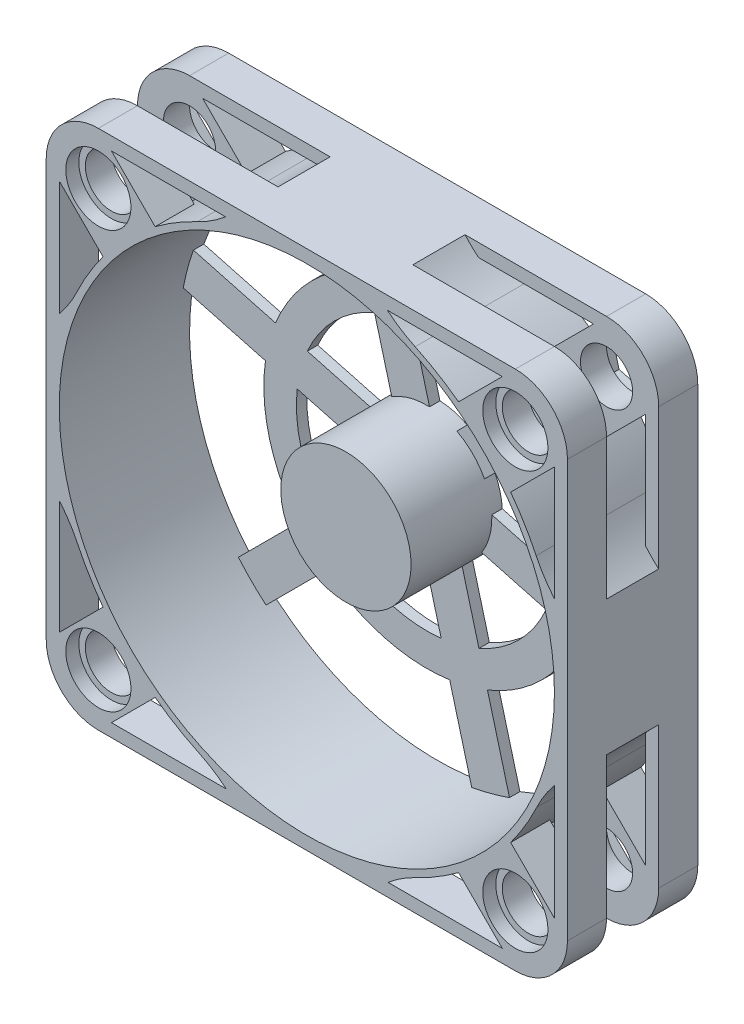
SolidWorks part; units mm, degrees
ref_plane "Plan de face" through (0, 0, 0) normal (0, 0, 1) x (1, 0, 0)
ref_plane "Plan de dessus" through (0, 0, 0) normal (0, 1, 0) x (1, 0, 0)
ref_plane "Plan de droite" through (0, 0, 0) normal (1, 0, 0) x (0, 0, -1)
sketch "Esquisse1" plane through (0, 0, 0) normal (0, 0, 1) x (1, 0, 0)
  line L0 (4.4333, 2.312) -> (14.4538, 12.3324)
  line L1 (16, -20) -> (-16, -20)
  line L2 (20, -16) -> (20, 16)
  line L3 (16, 20) -> (-16, 20)
  line L4 (-20, -16) -> (-20, 16)
  line L5 (20, -20) -> (-20, 20) construction
  line L6 (20, 20) -> (-20, -20) construction
  line L7 (2.312, 4.4333) -> (12.3324, 14.4538)
  line L8 (4.2189, -2.6834) -> (17.9071, -6.3511)
  line L9 (4.9954, 0.2144) -> (18.6835, -3.4533)
  line L10 (-0.2144, -4.9954) -> (3.4533, -18.6835)
  line L11 (2.6834, -4.2189) -> (6.3511, -17.9071)
  line L12 (-4.4333, -2.312) -> (-14.4538, -12.3324)
  line L13 (-2.312, -4.4333) -> (-12.3324, -14.4538)
  line L14 (-4.2189, 2.6834) -> (-17.9071, 6.3511)
  line L15 (-4.9954, -0.2144) -> (-18.6835, 3.4533)
  line L16 (0.2144, 4.9954) -> (-3.4533, 18.6835)
  line L17 (-2.6834, 4.2189) -> (-6.3511, 17.9071)
  arc A0 (-16, -20) -> (-20, -16) centre (-16, -16) cw
  arc A1 (16, -20) -> (20, -16) centre (16, -16) ccw
  arc A2 (20, 16) -> (16, 20) centre (16, 16) ccw
  arc A3 (-16, 20) -> (-20, 16) centre (-16, 16) ccw
  circle A4 centre (0, 0) radius 19
  circle A5 centre (-16, 16) radius 2
  circle A6 centre (16, 16) radius 2
  circle A7 centre (16, -16) radius 2
  circle A8 centre (-16, -16) radius 2
  circle A9 centre (0, 0) radius 5
  circle A10 centre (0, 0) radius 10
  circle A11 centre (0, 0) radius 12.5
  point P0 (0, 0)
  point P52 (0, 0)
  dimension "D3" = 4
  dimension "D4" = 38
  dimension "D5" = 4
  dimension "D6" = 4
  dimension "D7" = 4
  dimension "D8" = 4
  dimension "D9" = 10
  dimension "D12" = 25
  dimension "D13" = 20
  dimension "D1" = 40
  dimension "D2" = 40
  dimension "D10" = 3
  dimension "D11" = 6
extrude "Boss.-Extru.1" add sketch "Esquisse1" along normal blind 10 contours L3 A3 L4 A0 L1 A1 L2 A2 A8 A7 A6 A5 A4 | A11 L12 A4 L13 | L15 A11 L12 A10 | L12 A11 L13 A10 | L12 A10 L13 A9 | L13 A11 L10 A10 | L10 A11 L11 A10 | L10 A10 L11 A9 | A11 L10 A4 L11 | A9 | A11 L14 A4 L15 | L14 A11 L15 A10 | L14 A10 L15 A9 | L17 A11 L14 A10 | A11 L16 A4 L17 | L16 A11 L17 A10 | L16 A10 L17 A9 | L7 A11 L16 A10 | A11 L0 A4 L7 | L0 A10 L7 A9 | L0 A11 L7 A10 | L9 A11 L0 A10 | L8 A11 L9 A10 | A11 L8 A4 L9 | L11 A11 L8 A10 | L8 A10 L9 A9 region at (5.2629, 5.2629, 0) region at (0, 0, 0) region at (7.931, 7.931, 0) region at (10.651, 2.8539, 0) region at (7.1892, -1.9263, 0) region at (11.1193, 11.1193, 0) region at (2.8539, 10.651, 0) region at (10.8339, -2.9029, 0) region at (-1.9263, 7.1892, 0) region at (-2.9029, 10.8339, 0) region at (15.1892, -4.0699, 0) region at (7.797, -7.797, 0) region at (-4.0699, 15.1892, 0) region at (-7.797, 7.797, 0) region at (1.9263, -7.1892, 0) region at (2.9029, -10.8339, 0) region at (-7.1892, 1.9263, 0) region at (-10.8339, 2.9029, 0) region at (4.0699, -15.1892, 0) region at (-2.8539, -10.651, 0) region at (-15.1892, 4.0699, 0) region at (-10.651, -2.8539, 0) region at (-5.2629, -5.2629, 0) region at (-7.931, -7.931, 0) region at (-11.1193, -11.1193, 0) region at (0, -19.4343, 0)
sketch "Esquisse2" plane through (0, 0, 10) normal (0, 0, 1) x (1, 0, 0)
  circle A0 centre (0, 0) radius 19
  circle A1 centre (0, 0) radius 5
  dimension "D1" = 38
  dimension "D2" = 10
extrude "Enlèv. mat.-Extru.1" cut sketch "Esquisse2" against normal blind 9.2
sketch "Esquisse3" plane through (0, 0, 10) normal (0, 0, 1) x (1, 0, 0)
  line L0 (19, 15) -> (19, 4.3875)
  line L1 (20, -16) -> (20, 16) construction
  line L2 (4.3875, 19) -> (15, 19)
  line L3 (16, 20) -> (-16, 20) construction
  line L4 (15, 19) -> (11.6428, 15.6428)
  line L5 (7.7143, 9.8356) -> (12.3324, 14.4538) construction
  line L6 (19, 15) -> (15.6428, 11.6428)
  circle A0 centre (0, 0) radius 19.5
  arc A1 (15, 19) -> (19, 15) centre (15, 15) cw
  dimension "D1" = 39
  dimension "D4" = 4
  dimension "D2" = 1
  dimension "D3" = 1
extrude "Enlèv. mat.-Extru.2" cut sketch "Esquisse3" against normal blind 3 contours A0 L0 L6 | A0 L4 L2 region at (17.9389, 10.6636, 10) region at (10.6636, 17.9389, 10)
sketch "Esquisse4" plane through (0, 0, 10) normal (0, 0, 1) x (1, 0, 0)
  circle A0 centre (16, 16) radius 2.5
  dimension "D1" = 5
extrude "Enlèv. mat.-Extru.3" cut sketch "Esquisse4" against normal blind 1
pattern_circular "Répétition circulaire1" count 4 over 360 about axis through (0, 0, 10) along (0, 0, 1) of "Enlèv. mat.-Extru.2", "Enlèv. mat.-Extru.3"
sketch "Esquisse5" plane through (0, 0, 10) normal (0, 0, 1) x (1, 0, 0)
  circle A1 centre (0, 0) radius 5
  circle A2 centre (0, 0) radius 5
  dimension "D1" = 0
extrude "Enlèv. mat.-Extru.4" cut sketch "Esquisse5" against normal blind 3
ref_plane "Plan1" through (0, 0, 5) normal (0, 0, 1) x (1, 0, 0)
mirror "Symétrie1" about plane through (0, 0, 5) normal (0, 0, 1) of "Répétition circulaire1"
ref_plane "Plan2" through (18.8284, 18.8284, 0) normal (0.7071, 0.7071, 0) x (0.7071, -0.7071, 0)
sketch "Esquisse6" plane through (18.8284, 18.8284, 0) normal (0.7071, 0.7071, 0) x (0.7071, -0.7071, 0)
  line L0 (-2.8284, 0) -> (-25.4558, 0) construction
  line L1 (-10.5101, -3) -> (10.4566, -3)
  line L2 (-10.5101, -3) -> (-10.5101, -7)
  line L3 (-10.5101, -7) -> (10.4566, -7)
  line L4 (10.4566, -3) -> (10.4566, -7)
  dimension "D1" = 3
  dimension "D2" = 4
extrude "Enlèv. mat.-Extru.5" cut sketch "Esquisse6" against normal up to surface (10.1681 mm away) up to face at (17.5093, 8.1021, 1.5)
fillet "Congé2" radius 10 2 edges at (4.1826, 19.0462, 5) (19.0324, 4.2446, 5)
sketch "Esquisse7" plane through (0, 0, 0) normal (0, 0, -1) x (-1, 0, 0)
  line L0 (15, 19) -> (11.6428, 15.6428) construction
  line L1 (18.0412, 18.0412) -> (15.2529, 18.7884)
  line L2 (15.2529, 18.7884) -> (13.2116, 16.7471)
  line L3 (13.2116, 16.7471) -> (13.9588, 13.9588)
  line L4 (13.9588, 13.9588) -> (16.7471, 13.2116)
  line L5 (16.7471, 13.2116) -> (18.7884, 15.2529)
  line L6 (18.7884, 15.2529) -> (18.0412, 18.0412)
  circle A0 centre (16, 16) radius 2.5 construction
  dimension "D1" = 5
extrude "Enlèv. mat.-Extru.6" cut sketch "Esquisse7" against normal up to surface (1 mm away) up to face at (-18, 16, 1)
pattern_circular "Répétition circulaire3" count 4 over 360 about axis through (0, 0, 0) along (0, 0, 1) of "Congé2", "Enlèv. mat.-Extru.5", "Enlèv. mat.-Extru.6"
